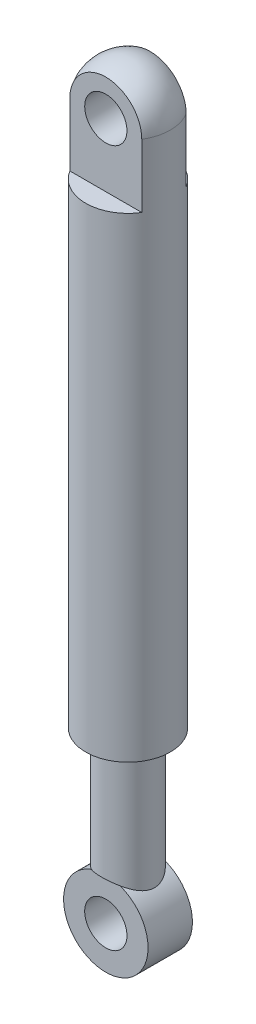
SolidWorks part; units mm, degrees
ref_plane "Front Plane" through (0, 0, 0) normal (0, 0, 1) x (1, 0, 0)
ref_plane "Top Plane" through (0, 0, 0) normal (0, 1, 0) x (1, 0, 0)
ref_plane "Right Plane" through (0, 0, 0) normal (1, 0, 0) x (0, 0, -1)
sketch "Sketch1" plane through (0, 0, 0) normal (0, 0, 1) x (1, 0, 0)
  line L4 (0, 0) -> (0, 51) construction
  line L5 (0, 0) -> (0, -15) construction
  circle A0 centre (0, 51) radius 2
  circle A1 centre (0, -15) radius 2
  point P6 (0, -14.1001)
  dimension "D1" = 4
  dimension "D2" = 4
  dimension "D3" = 66
  dimension "D4" = 15
sketch "Sketch3" plane through (0, 0, 0) normal (0, 0, 1) x (1, 0, 0)
  line L0 (0, 0) -> (4, 0)
  line L1 (4, 0) -> (4, 51)
  line L2 (0, 55) -> (0, 0)
  arc A0 (4, 51) -> (0, 55) centre (0, 51) ccw
  circle A1 centre (0, 51) radius 2 construction
  dimension "D1" = 4
revolve "Revolve2" add sketch "Sketch3" angle 360 about L4
sketch "Sketch4" plane through (0, 0, 0) normal (0, 0, 1) x (1, 0, 0)
  line L0 (2.5, 0) -> (2.5, -11.8775)
  line L1 (4.4, 0) -> (-4.4, 0) construction
  line L2 (0, 0) -> (0, -15) construction
  line L3 (0, -11) -> (0, 0)
  line L4 (0, 0) -> (2.5, 0)
  circle A2 centre (0, -15) radius 4
  circle A3 centre (0, -15) radius 2 construction
  point P11 (2.5, -11.8775)
  point P12 (0, -10.1276)
  point P16 (0, -11.0541)
  point P17 (0, -9.6644)
  point P18 (0, -11)
  dimension "D1" = 2.5
  dimension "D2" = 2
revolve "Revolve3" add sketch "Sketch4" angle 360 about L5 region at (1.2658, -5.6421, 0)
extrude "Cut-Extrude1" cut sketch "Sketch4<3>" against normal through all both and the other way through all contours A2
sketch "Sketch4<3>" plane through (0, 0, 0) normal (0, 0, 1) x (1, 0, 0) same geometry as "Sketch4"
extrude "Boss-Extrude1" add sketch "Sketch4<4>" along normal mid plane 4.2 contours A2
sketch "Sketch4<4>" plane through (0, 0, 0) normal (0, 0, 1) x (1, 0, 0) same geometry as "Sketch4"
sketch "Sketch5" plane through (0, 0, 0) normal (1, 0, 0) x (0, 0, -1)
  line L0 (-2.1, 54.4044) -> (-2.1, 45)
  line L1 (-2.1, 45) -> (-4, 45)
  line L2 (0, 4.4) -> (0, -4.4) construction
  line L3 (-4, 51) -> (-4, 0) construction
  arc A0 (4, 51) -> (-4, 51) centre (0, 51) ccw construction
  point P5 (-4, 47.2113)
  point P8 (-2.1, 54.4044)
  dimension "D1" = 2.1
  dimension "D2" = 10
extrude "Cut-Extrude2" cut sketch "Sketch5" against normal through all both and the other way through all flip side to cut contours L0 L1
mirror "Mirror1" about plane through (0, 0, 0) normal (0, 0, 1) of "Cut-Extrude2"
extrude "Cut-Extrude3" cut sketch "Sketch1" against normal through all both and the other way through all contours A0 | A1
